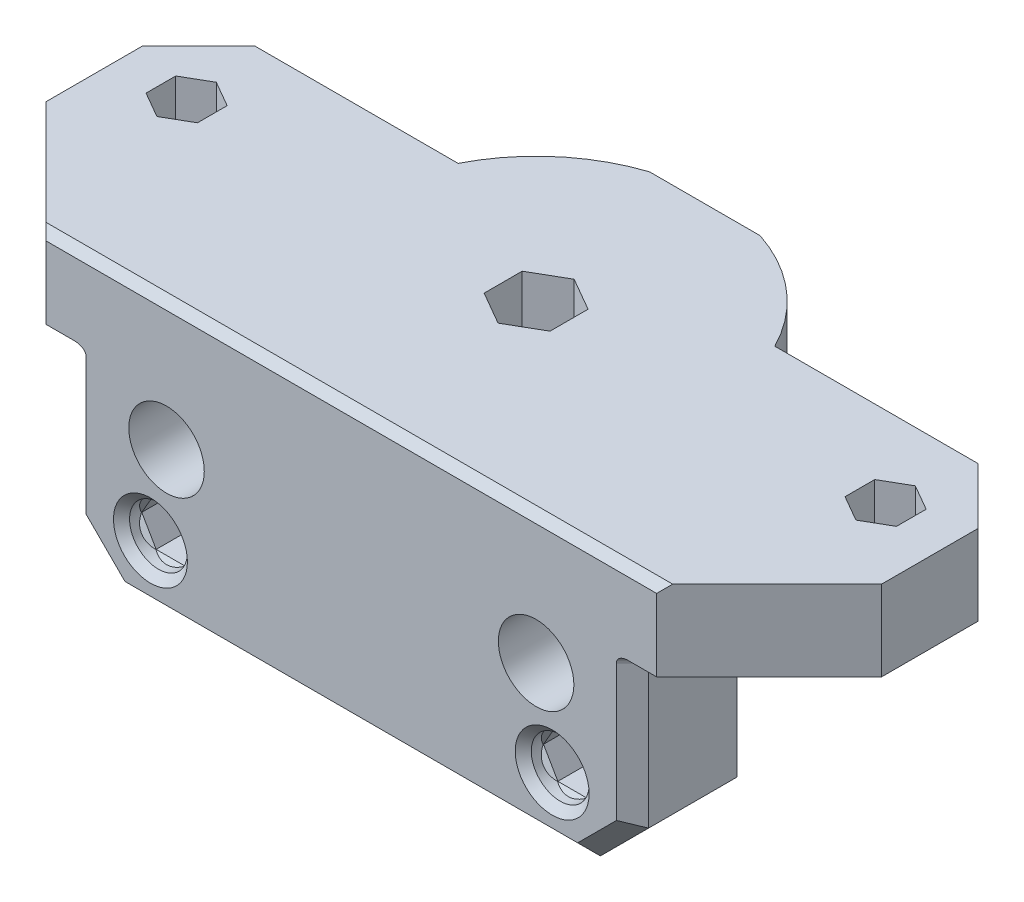
SolidWorks part; units mm, degrees
ref_plane "Front Plane" through (0, 0, 0) normal (0, 0, 1) x (1, 0, 0)
ref_plane "Top Plane" through (0, 0, 0) normal (0, 1, 0) x (1, 0, 0)
ref_plane "Right Plane" through (0, 0, 0) normal (1, 0, 0) x (0, 0, -1)
sketch "Sketch1" plane through (0, 0, 0) normal (0, 1, 0) x (1, 0, 0)
  circle A0 centre (0, 0) radius 8.05
  circle A1 centre (0, 0) radius 11.05
  dimension "D1" = 16.1
  dimension "D2" = 3
extrude "Boss-Extrude1" add sketch "Sketch1" along normal blind 3.5
sketch "Sketch2" plane through (0, 0, 0) normal (0, -1, 0) x (-1, 0, 0)
  circle A0 centre (0, 0) radius 6.05
  circle A1 centre (0, 0) radius 11.05
  dimension "D1" = 12.1
  dimension "D2" = 5
extrude "Boss-Extrude2" add sketch "Sketch2" along normal blind 5.9
sketch "Sketch3" plane through (0, -5.9, 0) normal (0, -1, 0) x (-1, 0, 0)
  circle A0 centre (0, 0) radius 8.05
  circle A1 centre (0, 0) radius 11.05
  dimension "D1" = 16.1
  dimension "D2" = 3
extrude "Boss-Extrude3" add sketch "Sketch3" along normal blind 3
sketch "Sketch5" plane through (0, 3.5, 0) normal (0, 1, 0) x (1, 0, 0)
  line L0 (9.8541, 5) -> (27, 5)
  line L1 (-27, -5) -> (-9.8541, -5)
  line L2 (-27, -5) -> (-27, 5)
  line L3 (-27, 5) -> (-9.8541, 5)
  line L4 (27, -5) -> (27, 5)
  line L5 (9.8541, -5) -> (27, -5)
  line L7 (0, 2.3671) -> (-2.05, 1.1836)
  line L8 (-2.05, 1.1836) -> (-2.05, -1.1836)
  line L9 (-2.05, -1.1836) -> (0, -2.3671)
  line L10 (0, -2.3671) -> (2.05, -1.1836)
  line L11 (2.05, -1.1836) -> (2.05, 1.1836)
  line L12 (2.05, 1.1836) -> (0, 2.3671)
  line L13 (-21.75, 1.8475) -> (-23.35, 0.9238)
  line L14 (-23.35, 0.9238) -> (-23.35, -0.9238)
  line L15 (-23.35, -0.9238) -> (-21.75, -1.8475)
  line L16 (-21.75, -1.8475) -> (-20.15, -0.9238)
  line L17 (-20.15, -0.9238) -> (-20.15, 0.9238)
  line L18 (-20.15, 0.9238) -> (-21.75, 1.8475)
  line L19 (21.75, 1.8475) -> (20.15, 0.9238)
  line L20 (20.15, 0.9238) -> (20.15, -0.9238)
  line L21 (20.15, -0.9238) -> (21.75, -1.8475)
  line L22 (21.75, -1.8475) -> (23.35, -0.9238)
  line L23 (23.35, -0.9238) -> (23.35, 0.9238)
  line L24 (23.35, 0.9238) -> (21.75, 1.8475)
  circle A0 centre (0, 0) radius 11.05 construction
  circle A1 centre (-21.75, 0) radius 1.5
  circle A2 centre (21.75, 0) radius 1.5
  circle A3 centre (0, 0) radius 2.05
  circle A4 centre (0, 0) radius 11.05
  circle A5 centre (0, 0) radius 2.05 construction
  circle A6 centre (-21.75, 0) radius 1.6 construction
  circle A7 centre (21.75, 0) radius 1.6 construction
  circle M6 centre (0, 0) radius 11.05
  circle M7 centre (0, 0) radius 8.05
  dimension "D5" = 3
  dimension "D8" = 4.1
  dimension "D11" = 22.1
  dimension "D12" = 4.1
  dimension "D13" = 3.2
  dimension "D14" = 3.2
  dimension "D1" = 10
  dimension "D2" = 54
  dimension "D3" = 27
  dimension "D4" = 5
  dimension "D6" = 5.25
  dimension "D9" = 5
  dimension "D10" = 27
  dimension "D7" = 2
extrude "Boss-Extrude5" add sketch "Sketch5" along normal blind 5 contours L3 L2 L1 A1 M6 | M6 M7 | L5 L4 L0 A2 M6 | A3 M7 region at (18.6586, 3.5, 0) region at (10.4429, 3.5, -2.4978) region at (-18.6586, 3.5, 0) region at (-7.8223, 3.5, 0)
sketch "Sketch6" plane through (0, 8.5, 0) normal (0, 1, 0) x (1, 0, 0)
  line L0 (-27, -5) -> (-9.8541, -5) construction
  line L1 (-15.5, -5) -> (-9.8541, -5)
  line L2 (-15.5, -5) -> (-15.5, -15)
  line L3 (-15.5, -15) -> (15.5, -15)
  line L4 (15.5, -5) -> (15.5, -15)
  line L5 (9.8541, -5) -> (15.5, -5)
  arc A1 (-9.8541, -5) -> (9.8541, -5) centre (0, 0) ccw
  dimension "D4" = 11.05
  dimension "D1" = 31
  dimension "D3" = 10
extrude "Boss-Extrude6" add sketch "Sketch6" against normal blind 28
sketch "Sketch7" plane through (0, 0, 15) normal (0, 0, 1) x (1, 0, 0)
  line L0 (-15.5, -19.5) -> (15.5, -19.5) construction
  line L1 (-15.5, -19.5) -> (-15.5, 8.5) construction
  circle A0 centre (-12, -16) radius 1.6
  circle A1 centre (12, -16) radius 1.6
  dimension "D4" = 3.2
  dimension "D1" = 3.5
  dimension "D2" = 3.5
  dimension "D3" = 2
extrude "Cut-Extrude1" cut sketch "Sketch7" against normal blind 10
sketch "Sketch19" plane through (0, 0, 15) normal (0, 0, 1) x (1, 0, 0)
  circle A0 centre (-12, -16) radius 2.25
  circle A1 centre (12, -16) radius 2.25
  dimension "D1" = 4.5
  dimension "D2" = 4.5
extrude "Cut-Extrude12" cut sketch "Sketch19" against normal blind 7.2
sketch "Sketch8" plane through (0, -19.5, 0) normal (0, -1, 0) x (-1, 0, 0)
  line L0 (15.5, -15) -> (-15.5, -15) construction
  line L1 (-8, -15) -> (8, -15)
  line L2 (-8, -15) -> (-8, -5)
  line L3 (-8, -5) -> (8, -5)
  line L4 (8, -15) -> (8, -5)
  circle A0 centre (0, 0) radius 12
  point P6 (0, -15)
  line M6 (15.5, -5) -> (9.8541, -5)
  arc M7 (9.8541, -5) -> (-9.8541, -5) centre (0, 0) cw
  line M8 (-9.8541, -5) -> (-15.5, -5)
  line M10 (-15.5, -15) -> (15.5, -15)
  dimension "D4" = 24
  dimension "D1" = 10
  dimension "D2" = 16
  dimension "D3" = 0
extrude "Cut-Extrude2" cut sketch "Sketch8" against normal blind 7 contours A0 L2 L4 M10 | L2 A0 L4 M7 | L4 L3 L2 M7 | A0 L2 M8 M7 | L4 A0 M6 M7 region at (0, -19.5, 12.9198) region at (9.3108, -19.5, 6.7422) region at (7.8341, -19.5, 8.2834) region at (-9.3108, -19.5, 6.7422) region at (0, -19.5, 7.5931)
ref_plane "Plane1" through (0, 0, 0.1) normal (0, 0, 1) x (1, 0, 0)
sketch "Sketch11" plane through (0, 0, 0.1) normal (0, 0, 1) x (1, 0, 0)
  line L0 (9.8541, 3.5) -> (27, 3.5) construction
  line L1 (33.7519, -27.3661) -> (-35.342, -27.3661)
  line L2 (33.7519, -27.3661) -> (33.7519, 3.5)
  line L3 (33.7519, 3.5) -> (-35.342, 3.5)
  line L4 (-35.342, -27.3661) -> (-35.342, 3.5)
  dimension "D1" = 0
extrude "Cut-Extrude4" cut sketch "Sketch11" against normal through all
sketch "Sketch12" plane through (0, 0, 15) normal (0, 0, 1) x (1, 0, 0)
  line L0 (-15.5, -19.5) -> (-15.5, 8.5) construction
  line L1 (15.5, -19.5) -> (15.5, 8.5) construction
  line L2 (-15.5, 8.5) -> (15.5, 8.5) construction
  circle A0 centre (-11.5, 0.5) radius 1.65
  circle A1 centre (11.5, 0.5) radius 1.65
  dimension "D1" = 3.3
  dimension "D2" = 3.3
  dimension "D3" = 4
  dimension "D4" = 4
  dimension "D5" = 8
  dimension "D6" = 8
extrude "Cut-Extrude5" cut sketch "Sketch12" against normal through all
sketch "Sketch13" plane through (0, 0, 15) normal (0, 0, 1) x (1, 0, 0)
  circle A0 centre (-11.5, 0.5) radius 2.25
  circle A1 centre (11.5, 0.5) radius 2.25
  dimension "D1" = 4.5
  dimension "D2" = 4.5
extrude "Cut-Extrude6" cut sketch "Sketch13" against normal blind 4.2
sketch "Sketch18" plane through (0, 3.5, 0) normal (0, -1, 0) x (-1, 0, 0)
  line L1 (-21.75, 3.2332) -> (-24.55, 1.6166)
  line L2 (-24.55, 1.6166) -> (-24.55, -1.6166)
  line L3 (-24.55, -1.6166) -> (-21.75, -3.2332)
  line L4 (-21.75, -3.2332) -> (-18.95, -1.6166)
  line L5 (-18.95, -1.6166) -> (-18.95, 1.6166)
  line L6 (-18.95, 1.6166) -> (-21.75, 3.2332)
  line L7 (21.811, 3.1274) -> (19.011, 1.5108)
  line L8 (19.011, 1.5108) -> (19.011, -1.7223)
  line L9 (19.011, -1.7223) -> (21.811, -3.3389)
  line L10 (21.811, -3.3389) -> (24.611, -1.7223)
  line L11 (24.611, -1.7223) -> (24.611, 1.5108)
  line L12 (24.611, 1.5108) -> (21.811, 3.1274)
  circle A0 centre (-21.75, 0) radius 2.8 construction
  circle A1 centre (21.811, -0.1057) radius 2.8 construction
  dimension "D1" = 5.6
  dimension "D2" = 5.6
extrude "Cut-Extrude11" cut sketch "Sketch18" against normal blind 2
sketch "Sketch20" plane through (0, 0, 15) normal (0, 0, 1) x (1, 0, 0)
  line L0 (-15.5, -19.5) -> (-15.5, 8.5) construction
  line L1 (15.5, -19.5) -> (-15.5, -19.5)
  line L2 (15.5, -19.5) -> (15.5, -8.9)
  line L3 (15.5, -8.9) -> (-15.5, -8.9)
  line L4 (-15.5, -19.5) -> (-15.5, -8.9)
  line L5 (8, -8.9) -> (-8, -8.9) construction
  dimension "D1" = 0
extrude "Cut-Extrude13" cut sketch "Sketch20" against normal blind 3
sketch "Sketch25" plane through (0, 0, 5) normal (0, 0, 1) x (1, 0, 0)
  line L1 (15.5, 8.5) -> (27, 8.5)
  line L2 (15.5, 8.5) -> (15.5, 3.5)
  line L3 (15.5, 3.5) -> (27, 3.5)
  line L4 (27, 8.5) -> (27, 3.5)
  line L5 (-15.5, 3.5) -> (-27, 3.5)
  line L6 (-15.5, 3.5) -> (-15.5, 8.5)
  line L7 (-15.5, 8.5) -> (-27, 8.5)
  line L8 (-27, 3.5) -> (-27, 8.5)
extrude "Boss-Extrude7" add sketch "Sketch25" along normal blind 3.3
sketch "草图1" plane through (0, 0, 15) normal (0, 0, 1) x (1, 0, 0)
  line L1 (-15.5, 8.5) -> (15.5, 8.5)
  line L2 (-15.5, 8.5) -> (-15.5, -19.5)
  line L3 (-15.5, -19.5) -> (15.5, -19.5)
  line L4 (15.5, 8.5) -> (15.5, -19.5)
extrude "切除-拉伸1" cut sketch "草图1" against normal blind 3.5
sketch "草图2" plane through (0, -19.5, 0) normal (0, -1, 0) x (-1, 0, 0)
  line L1 (15.5, -11.5) -> (-15.5, -11.5)
  line L2 (15.5, -11.5) -> (15.5, -5)
  line L3 (15.5, -5) -> (-15.5, -5)
  line L4 (-15.5, -11.5) -> (-15.5, -5)
extrude "切除-拉伸2" cut sketch "草图2" against normal up to surface (10.6 mm away) up to face at (0, -8.9, 4.0897)
sketch "草图3" plane through (0, 0, 11.5) normal (0, 0, 1) x (1, 0, 0)
  circle A0 centre (-11.5, 0.5) radius 2.35
  circle A1 centre (11.5, 0.5) radius 2.35
  dimension "D1" = 4.7
  dimension "D2" = 4.7
extrude "切除-拉伸3" cut sketch "草图3" against normal blind 3.8
chamfer "倒角1" distance 0.7 angle 45 2 edges at (-9.85, 0.5, 7.7) (13.15, 0.5, 7.7)
sketch "草图4" plane through (0, 0, 11.5) normal (0, 0, 1) x (1, 0, 0)
  line L0 (-15.5, 8.5) -> (-15.5, -8.9) construction
  line L1 (-15.5, -8.9) -> (15.5, -8.9) construction
  line L2 (15.5, -8.9) -> (15.5, 8.5) construction
  circle A0 centre (-12.5, -4.9) radius 1.8
  circle A1 centre (12.5, -4.9) radius 1.8
  dimension "D1" = 3.6
  dimension "D3" = 4
  dimension "D4" = 3.6
  dimension "D5" = 4
  dimension "D6" = 3
  dimension "D2" = 3
extrude "切除-拉伸4" cut sketch "草图4" against normal blind 1
sketch "草图10" plane through (0, 0, 10.5) normal (0, 0, 1) x (1, 0, 0)
  line L1 (-10.7102, -4.9) -> (-11.6051, -3.35)
  line L2 (-11.6051, -3.35) -> (-13.3949, -3.35)
  line L3 (-13.3949, -3.35) -> (-14.2898, -4.9)
  line L4 (-14.2898, -4.9) -> (-13.3949, -6.45)
  line L5 (-13.3949, -6.45) -> (-11.6051, -6.45)
  line L6 (-11.6051, -6.45) -> (-10.7102, -4.9)
  line L7 (14.2898, -4.9) -> (13.3949, -3.35)
  line L8 (13.3949, -3.35) -> (11.6051, -3.35)
  line L9 (11.6051, -3.35) -> (10.7102, -4.9)
  line L10 (10.7102, -4.9) -> (11.6051, -6.45)
  line L11 (11.6051, -6.45) -> (13.3949, -6.45)
  line L12 (13.3949, -6.45) -> (14.2898, -4.9)
  circle A0 centre (-12.5, -4.9) radius 1.55 construction
  circle A1 centre (12.5, -4.9) radius 1.55 construction
  dimension "D1" = 3.1
  dimension "D2" = 3.1
extrude "切除-拉伸7" cut sketch "草图10" against normal through all
chamfer "倒角7" distance 0.25 angle 45 6 edges at (-12.5, -6.45, 10.5) (-13.8423, -5.675, 10.5) (-11.1577, -5.675, 10.5) (-11.1577, -4.125, 10.5) (-13.8423, -4.125, 10.5) (-12.5, -3.35, 10.5)
chamfer "倒角8" distance 0.25 angle 45 6 edges at (13.8423, -5.675, 10.5) (12.5, -6.45, 10.5) (11.1577, -5.675, 10.5) (13.8423, -4.125, 10.5) (11.1577, -4.125, 10.5) (12.5, -3.35, 10.5)
ref_axis "基准轴1" through (9.8541, 8.5, -5) along (1, 0, 0)
ref_plane "基准面1" through (0, 6.75, -6.75) normal (0, 0.7071, -0.7071) x (1, 0, 0)
ref_plane "基准面2" through (0, 9.5006, -9.5006) normal (0, 0.7071, -0.7071) x (1, 0, 0)
sketch "草图11" plane through (0, 9.5006, -9.5006) normal (0, 0.7071, -0.7071) x (1, 0, 0)
  line L1 (-14.5081, 8.4609) -> (16.7, 8.4609)
  line L2 (-14.5081, 8.4609) -> (-14.5081, -7.7078)
  line L3 (-14.5081, -7.7078) -> (16.7, -7.7078)
  line L4 (16.7, 8.4609) -> (16.7, -7.7078)
extrude "切除-拉伸9" cut sketch "草图11" along normal through all
sketch "草图5" plane through (-15.5, 0, 0) normal (-1, 0, 0) x (0, 0, 1)
  line L1 (5, 3.5) -> (11.5, 3.5)
  line L2 (5, 3.5) -> (5, -8.9)
  line L3 (5, -8.9) -> (11.5, -8.9)
  line L4 (11.5, 3.5) -> (11.5, -8.9)
  line L5 (8.3, 8.5) -> (11.5, 8.5)
  line L6 (8.3, 8.5) -> (8.3, 3.5)
  line L7 (8.3, 3.5) -> (11.5, 3.5)
  line L8 (11.5, 8.5) -> (11.5, 3.5)
  line M1 (5, 3.5) -> (5, -8.9)
  line M2 (5, -8.9) -> (11.5, -8.9)
  line M3 (11.5, -8.9) -> (11.5, 8.5)
  line M4 (11.5, 8.5) -> (8.3, 8.5)
  line M5 (8.3, 8.5) -> (8.3, 3.5)
  line M6 (8.3, 3.5) -> (5, 3.5)
extrude "凸台-拉伸1" add sketch "草图5" along normal blind 2 contours L1 M6 M1 M2 M3 | L1 M5 M3 M4 region at (-15.5, -2.7, 8.25) region at (-15.5, 6, 9.9)
sketch "草图6" plane through (15.5, 0, 0) normal (1, 0, 0) x (0, 0, -1)
  line L9 (-5, 3.5) -> (-11.5, 3.5)
  line L10 (-5, 3.5) -> (-5, -8.9)
  line L11 (-5, -8.9) -> (-11.5, -8.9)
  line L12 (-11.5, 3.5) -> (-11.5, -8.9)
  line L13 (-11.5, 8.5) -> (-8.3, 8.5)
  line L14 (-11.5, 8.5) -> (-11.5, 3.5)
  line L15 (-11.5, 3.5) -> (-8.3, 3.5)
  line L16 (-8.3, 8.5) -> (-8.3, 3.5)
  line M1 (-11.5, 8.5) -> (-11.5, -8.9)
  line M2 (-11.5, -8.9) -> (-5, -8.9)
  line M3 (-5, -8.9) -> (-5, 3.5)
  line M4 (-5, 3.5) -> (-8.3, 3.5)
  line M5 (-8.3, 3.5) -> (-8.3, 8.5)
  line M6 (-8.3, 8.5) -> (-11.5, 8.5)
extrude "凸台-拉伸2" add sketch "草图6" along normal blind 2 contours L9 M5 M6 M1 | L9 M4 M1 M2 M3 region at (15.5, -2.7, 8.25) region at (15.5, 6, 9.9)
chamfer "倒角3" distance 4.5 angle 45 2 edges at (27, 6, -5) (-27, 6, -5)
sketch "草图8" plane through (0, 0, 8.3) normal (0, 0, 1) x (1, 0, 0)
  line L1 (-27, 8.5) -> (-17.5, 8.5)
  line L2 (-27, 8.5) -> (-27, 3.5)
  line L3 (-27, 3.5) -> (-17.5, 3.5)
  line L4 (-17.5, 8.5) -> (-17.5, 3.5)
  line L5 (27, 8.5) -> (17.5, 8.5)
  line L6 (27, 8.5) -> (27, 3.5)
  line L7 (27, 3.5) -> (17.5, 3.5)
  line L8 (17.5, 8.5) -> (17.5, 3.5)
extrude "凸台-拉伸3" add sketch "草图8" along normal up to surface (3.2 mm away) up to face at (-10.7, -4.9, 11.5)
chamfer "倒角4" distance 8 angle 45 2 edges at (27, 6, 11.5) (-27, 6, 11.5)
sketch "草图9" plane through (0, 8.5, 0) normal (0, 1, 0) x (1, 0, 0)
  line L0 (-27, -3.5) -> (-27, 0.5) construction
  line L1 (-32.8717, 7.8341) -> (-26, 7.8341)
  line L2 (-32.8717, 7.8341) -> (-32.8717, -8.0819)
  line L3 (-32.8717, -8.0819) -> (-26, -8.0819)
  line L4 (-26, 7.8341) -> (-26, -8.0819)
  line L5 (30.9516, 7.0761) -> (26, 7.0761)
  line L6 (30.9516, 7.0761) -> (30.9516, -6.5661)
  line L7 (30.9516, -6.5661) -> (26, -6.5661)
  line L8 (26, 7.0761) -> (26, -6.5661)
  line L9 (27, -3.5) -> (27, 0.5) construction
  point P12 (27, -1.5)
  dimension "D1" = 1
  dimension "D2" = 1
extrude "切除-拉伸6" cut sketch "草图9" against normal through all
chamfer "倒角5" distance 3 angle 45 2 edges at (17.5, -8.9, 8.25) (-17.5, -8.9, 8.25)
chamfer "倒角6" distance 1 angle 45 5 edges at (17.5, -1.2, 11.5) (16, -7.4, 11.5) (0, -8.9, 11.5) (-16, -7.4, 11.5) (-17.5, -1.2, 11.5)
fillet "圆角2" radius 0.5 2 edges at (-17, 3.5, 11) (17, 3.5, 11)
chamfer "倒角9" distance 0.5 angle 45 2 edges at (-10.7, -4.9, 11.5) (14.3, -4.9, 11.5)
chamfer "倒角10" distance 0.5 angle 45 1 edges at (0, 8.5, 11.5)
equation "\"D3@Sketch5\"=\"D2@Sketch5\"/2"
equation "\"D4@Sketch5\"=\"D1@Sketch5\"/2"
equation "\"D6@Sketch5\"=\"D2@Sketch5\"/2-43.5/2"
equation "\"D9@Sketch5\"=\"D4@Sketch5\""
equation "\"D10@Sketch5\"=\"D3@Sketch5\""
equation "\"D1@Sketch6\"=30+1"
